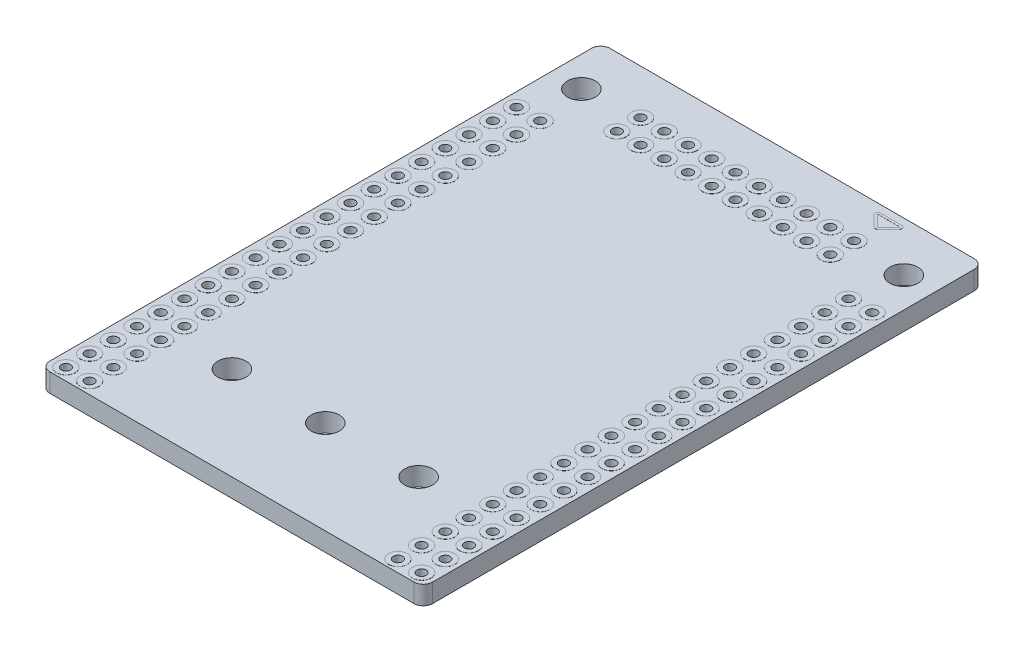
SolidWorks part; units mm, degrees
ref_plane "Front Plane" through (0, 0, 0) normal (0, 0, 1) x (1, 0, 0)
ref_plane "Top Plane" through (0, 0, 0) normal (0, 1, 0) x (1, 0, 0)
ref_plane "Right Plane" through (0, 0, 0) normal (1, 0, 0) x (0, 0, -1)
sketch "Sketch1" plane through (0, 0, 0) normal (0, 1, 0) x (1, 0, 0)
  line L1 (-19.5, -30) -> (19.5, -30)
  line L2 (-20.5, -29) -> (-20.5, 29)
  line L3 (-19.5, 30) -> (19.5, 30)
  line L4 (20.5, -29) -> (20.5, 29)
  line L5 (-20.5, -30) -> (20.5, 30) construction
  line L6 (-20.5, 30) -> (20.5, -30) construction
  arc A0 (-19.5, -30) -> (-20.5, -29) centre (-19.5, -29) cw
  arc A1 (19.5, -30) -> (20.5, -29) centre (19.5, -29) ccw
  arc A2 (19.5, 30) -> (20.5, 29) centre (19.5, 29) cw
  arc A3 (-20.5, 29) -> (-19.5, 30) centre (-19.5, 29) cw
  point P0 (0, 0)
  dimension "D3" = 1
  dimension "D1" = 41
  dimension "D2" = 60
extrude "Boss-Extrude1" add sketch "Sketch1" along normal blind 2
sketch "Sketch4" plane through (0, 2, 0) normal (0, 1, 0) x (1, 0, 0)
  line L0 (-19.5, -30) -> (19.5, -30) construction
  circle A0 centre (0, -20) radius 1.5
  circle A1 centre (-10, -20) radius 1.5
  circle A2 centre (10, -20) radius 1.5
  dimension "D1" = 3
  dimension "D2" = 10
  dimension "D3" = 10
  dimension "D4" = 10
extrude "Cut-Extrude2" cut sketch "Sketch4" against normal through all
sketch "Sketch2" plane through (0, 2, 0) normal (0, 1, 0) x (1, 0, 0)
  circle A0 centre (-1.27, 25.2) radius 0.5
  circle A1 centre (-1.27, 25.2) radius 1
  circle A2 centre (0, -20) radius 1.5 construction
  dimension "D1" = 1
  dimension "D2" = 0.5
  dimension "D3" = 45.2
  dimension "D4" = 1.27
extrude "Boss-Extrude2" add sketch "Sketch2" along normal blind 0.01
sketch "Sketch3" plane through (0, 2, 0) normal (0, 1, 0) x (1, 0, 0)
  circle A0 centre (-1.27, 25.2) radius 0.5
extrude "Cut-Extrude1" cut sketch "Sketch3" against normal through all both and the other way through all
pattern_linear "LPattern3" count 2 spacing 2.54 along (0, 0, 1) of "Boss-Extrude2", "Cut-Extrude1"
pattern_linear "LPattern4" count 5 spacing 2.54 along (-1, 0, 0) of "LPattern3"
pattern_linear "LPattern5" count 6 spacing 2.54 along (1, 0, 0) of "LPattern3"
sketch "Sketch5" plane through (0, 2, 0) normal (0, 1, 0) x (1, 0, 0)
  line L2 (-20.5, 0) -> (0, 0) construction
  line L3 (-20.5, 29) -> (-20.5, -29) construction
  line L4 (0, 0) -> (0, -30) construction
  line L5 (-19.5, -30) -> (19.5, -30) construction
  circle A0 centre (-19.05, -28.73) radius 0.5
  circle A1 centre (-19.05, -28.73) radius 1
  dimension "D1" = 1
  dimension "D2" = 0.5
  dimension "D3" = 19.05
  dimension "D4" = 28.73
extrude "Boss-Extrude3" add sketch "Sketch5" along normal blind 0.01
sketch "Sketch6" plane through (0, 2, 0) normal (0, 1, 0) x (1, 0, 0)
  circle A0 centre (-19.05, -28.73) radius 0.5
extrude "Cut-Extrude3" cut sketch "Sketch6" against normal through all both and the other way through all
pattern_linear "LPattern6" count 2 spacing 2.54 along (1, 0, 0) of "Boss-Extrude3", "Cut-Extrude3"
pattern_linear "LPattern7" count 20 spacing 2.54 along (0, 0, -1) of "LPattern6"
sketch "Sketch7" plane through (0, 2, 0) normal (0, 1, 0) x (1, 0, 0)
  line L0 (-19.5, -30) -> (19.5, -30) construction
  line L1 (20.5, -29) -> (20.5, 29) construction
  line L2 (0, 0) -> (0, -30) construction
  line L3 (0, 0) -> (20.5, 0) construction
  circle A0 centre (19.05, -28.73) radius 0.5
  circle A1 centre (19.05, -28.73) radius 1
  dimension "D1" = 1
  dimension "D2" = 0.5
  dimension "D3" = 19.05
  dimension "D4" = 28.73
extrude "Boss-Extrude4" add sketch "Sketch7" along normal blind 0.01
sketch "Sketch8" plane through (0, 2, 0) normal (0, 1, 0) x (1, 0, 0)
  circle A0 centre (19.05, -28.73) radius 0.5
extrude "Cut-Extrude4" cut sketch "Sketch8" against normal through all both and the other way through all
pattern_linear "LPattern8" count 2 spacing 2.54 along (-1, 0, 0) of "Boss-Extrude4", "Cut-Extrude4"
pattern_linear "LPattern9" count 20 spacing 2.54 along (0, 0, -1) of "LPattern8"
sketch "Sketch10" plane through (0, 2, 0) normal (0, 1, 0) x (1, 0, 0)
  line L0 (11.4654, 27.7354) -> (12.5946, 28.8646)
  line L1 (12.5593, 28.95) -> (10.3007, 28.95)
  line L2 (10.2654, 28.8646) -> (11.3946, 27.7354)
  line L3 (11.43, 25.2) -> (11.43, 27.7) construction
  line L4 (11.6421, 27.5586) -> (12.7714, 28.6879)
  line L5 (12.5593, 29.2) -> (10.3007, 29.2)
  line L6 (10.0886, 28.6879) -> (11.2179, 27.5586)
  arc A0 (11.4654, 27.7354) -> (11.3946, 27.7354) centre (11.43, 27.7707) cw
  arc A1 (12.5946, 28.8646) -> (12.5593, 28.95) centre (12.5593, 28.9) ccw
  arc A2 (10.3007, 28.95) -> (10.2654, 28.8646) centre (10.3007, 28.9) ccw
  arc A3 (12.7714, 28.6879) -> (12.5593, 29.2) centre (12.5593, 28.9) ccw
  arc A4 (10.3007, 29.2) -> (10.0886, 28.6879) centre (10.3007, 28.9) ccw
  arc A5 (11.6421, 27.5586) -> (11.2179, 27.5586) centre (11.43, 27.7707) cw
  point P10 (12.68, 28.95)
  point P13 (10.18, 28.95)
  dimension "D4" = 0.05
  dimension "D1" = 45
  dimension "D2" = 2.5
  dimension "D3" = 2.5
  dimension "D5" = 0.25
extrude "Boss-Extrude5" add sketch "Sketch10" along normal blind 0.01
sketch "Sketch11" plane through (0, 2, 0) normal (0, 1, 0) x (1, 0, 0)
  line L0 (0, -20) -> (0, 0) construction
  circle A0 centre (-17.27, 24.7) radius 1.5
  circle A1 centre (-10, -20) radius 1.5 construction
  circle A2 centre (0, -20) radius 1.5 construction
  circle A3 centre (17.27, 24.7) radius 1.5
  dimension "D2" = 17.27
  dimension "D3" = 3
  dimension "D1" = 44.7
extrude "Cut-Extrude5" cut sketch "Sketch11" against normal through all
